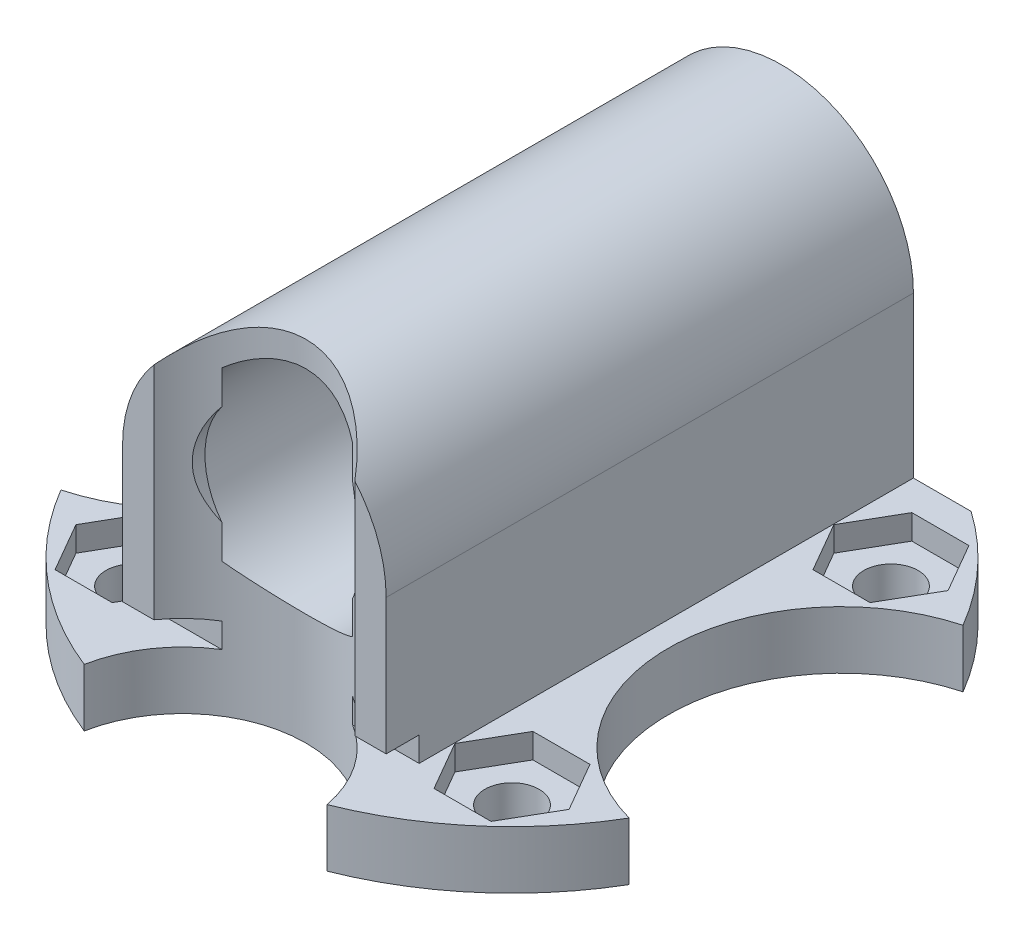
SolidWorks part; units mm, degrees
ref_plane "Front Plane" through (0, 0, 0) normal (0, 0, 1) x (1, 0, 0)
ref_plane "Top Plane" through (0, 0, 0) normal (0, 1, 0) x (1, 0, 0)
ref_plane "Right Plane" through (0, 0, 0) normal (1, 0, 0) x (0, 0, -1)
sketch "Sketch1" plane through (0, 0, 0) normal (0, 1, 0) x (1, 0, 0)
  line L0 (-23.7557, 20.1202) -> (-0.7557, -2.8798) construction
  line L1 (-0.7557, 20.1202) -> (-23.7557, -2.8798) construction
  circle A0 centre (-23.7557, 20.1202) radius 1.65
  circle A1 centre (-0.7557, 20.1202) radius 1.65
  circle A2 centre (-23.7557, -2.8798) radius 1.65
  circle A3 centre (-0.7557, -2.8798) radius 1.65
  circle A4 centre (-12.2557, 8.6202) radius 20
  point P4 (-12.2557, 8.6202)
  dimension "D1" = 3.3
  dimension "D2" = 23
  dimension "D7" = 40
  dimension "D3" = 23
  dimension "D4" = 23
  dimension "D5" = 23
  dimension "D6" = 23
extrude "Boss-Extrude2" add sketch "Sketch1" along normal blind 3.5
ref_axis "Axis1" through (-12.2557, 3.5, -8.6202) along (0, -1, 0)
sketch "Sketch3" plane through (0, 3.5, 0) normal (0, 1, 0) x (1, 0, 0)
  line L0 (-23.7557, 24.9832) -> (-0.7557, 24.9832)
  circle A0 centre (-12.2557, 8.6202) radius 20 construction
  dimension "D1" = 23
extrude "Cut-Extrude1" cut sketch "Sketch3" against normal through all and the other way through all
sketch "Sketch4" plane through (0, 0, -24.9832) normal (0, 0, -1) x (-1, 0, 0)
  line L0 (0.7557, 3.5) -> (0.7557, 0) construction
  line L1 (4.2557, 13.2251) -> (4.2557, 3.5)
  line L2 (0.7557, 3.5) -> (23.7557, 3.5) construction
  line L3 (20.2557, 13.2251) -> (20.2557, 3.5)
  line L4 (20.2557, 3.5) -> (4.2557, 3.5)
  circle A0 centre (12.2557, 13.2251) radius 6.45
  arc A1 (20.2557, 13.2251) -> (4.2557, 13.2251) centre (12.2557, 13.2251) ccw
  dimension "D1" = 12.9
  dimension "D2" = 11.5
  dimension "D3" = 16
extrude "Boss-Extrude3" add sketch "Sketch4" against normal blind 30
sketch "Sketch5" plane through (0, 0, 5.0168) normal (0, 0, 1) x (1, 0, 0)
  line L0 (-20.2557, 13.2251) -> (-20.2557, 5)
  line L1 (-20.2557, 3.5) -> (-20.2557, 13.2251) construction
  line L2 (-4.2557, 13.2251) -> (-4.2557, 5)
  line L3 (-4.2557, 13.2251) -> (-4.2557, 3.5) construction
  line L4 (-4.2557, 5) -> (-20.2557, 5)
  circle A0 centre (-12.2557, 13.2251) radius 5
  arc A1 (-4.2557, 13.2251) -> (-20.2557, 13.2251) centre (-12.2557, 13.2251) ccw
  dimension "D1" = 10
extrude "Boss-Extrude4" add sketch "Sketch5" along normal blind 2
sketch "Sketch6" plane through (0, 0, 0) normal (0, -1, 0) x (1, 0, 0)
  line L1 (-22.0236, -17.1202) -> (-25.4877, -17.1202)
  line L2 (-25.4877, -17.1202) -> (-27.2198, -20.1202)
  line L3 (-27.2198, -20.1202) -> (-25.4877, -23.1202)
  line L4 (-25.4877, -23.1202) -> (-22.0236, -23.1202)
  line L5 (-22.0236, -23.1202) -> (-20.2916, -20.1202)
  line L6 (-20.2916, -20.1202) -> (-22.0236, -17.1202)
  line L7 (-22.0236, -0.1202) -> (-20.2916, 2.8798)
  line L8 (-20.2916, 2.8798) -> (-22.0236, 5.8798)
  line L9 (-22.0236, 5.8798) -> (-25.4877, 5.8798)
  line L10 (-25.4877, 5.8798) -> (-27.2198, 2.8798)
  line L11 (-27.2198, 2.8798) -> (-25.4877, -0.1202)
  line L12 (-25.4877, -0.1202) -> (-22.0236, -0.1202)
  line L13 (0.9764, -0.1202) -> (2.7084, 2.8798)
  line L14 (2.7084, 2.8798) -> (0.9764, 5.8798)
  line L15 (0.9764, 5.8798) -> (-2.4877, 5.8798)
  line L16 (-2.4877, 5.8798) -> (-4.2198, 2.8798)
  line L17 (-4.2198, 2.8798) -> (-2.4877, -0.1202)
  line L18 (-2.4877, -0.1202) -> (0.9764, -0.1202)
  line L19 (0.9764, -17.1202) -> (-2.4877, -17.1202)
  line L20 (-2.4877, -17.1202) -> (-4.2198, -20.1202)
  line L21 (-4.2198, -20.1202) -> (-2.4877, -23.1202)
  line L22 (-2.4877, -23.1202) -> (0.9764, -23.1202)
  line L23 (0.9764, -23.1202) -> (2.7084, -20.1202)
  line L24 (2.7084, -20.1202) -> (0.9764, -17.1202)
  circle A0 centre (-23.7557, -20.1202) radius 3 construction
  circle A1 centre (-23.7557, 2.8798) radius 3 construction
  circle A2 centre (-0.7557, 2.8798) radius 3 construction
  circle A3 centre (-0.7557, -20.1202) radius 3 construction
  dimension "D1" = 6
  dimension "D2" = 6
  dimension "D3" = 6
  dimension "D4" = 6
extrude "Cut-Extrude2" cut sketch "Sketch6" along normal blind 1.5 from offset 3.5 offset against normal yes
sketch "Sketch7" plane through (0, 0, 0) normal (0, -1, 0) x (1, 0, 0)
  circle A0 centre (-32.2557, -8.6202) radius 10.5
  arc A1 (-0.7557, -24.9832) -> (-23.7557, -24.9832) centre (-12.2557, -8.6202) ccw construction
  circle A2 centre (7.7443, -8.6202) radius 10.5
  circle A3 centre (-12.2557, 11.3798) radius 7.5
  dimension "D1" = 21
  dimension "D2" = 21
  dimension "D3" = 15
extrude "Cut-Extrude3" cut sketch "Sketch7" against normal through all
